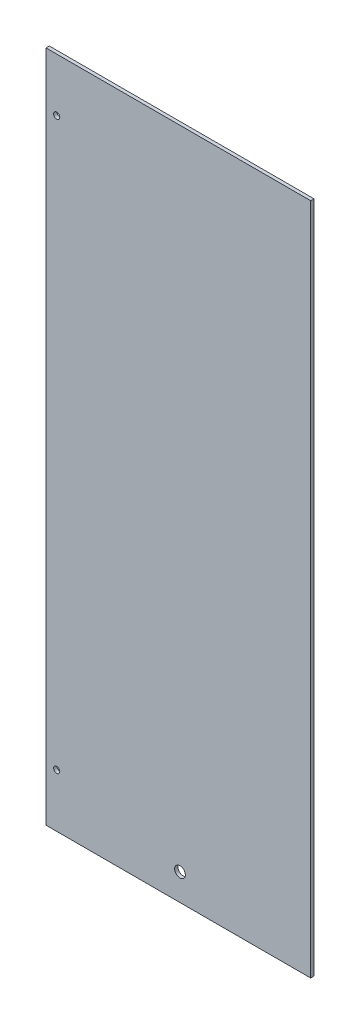
SolidWorks part; units mm, degrees
material "6061 Alloy"
ref_plane "Front" through (0, 0, 0) normal (0, 0, 1) x (1, 0, 0)
ref_plane "Top" through (0, 0, 0) normal (0, 1, 0) x (1, 0, 0)
ref_plane "Right" through (0, 0, 0) normal (1, 0, 0) x (0, 0, -1)
sketch "Sketch1" plane through (0, 0, 0) normal (0, 0, 1) x (1, 0, 0)
  line L1 (0, 0) -> (126.0475, 0)
  line L2 (0, 0) -> (0, 320.675)
  line L3 (0, 320.675) -> (126.0475, 320.675)
  line L4 (126.0475, 0) -> (126.0475, 320.675)
  dimension "D1" = 320.675
  dimension "D2" = 126.0475
extrude "Main Plate" add sketch "Sketch1" along normal blind 1.5875
sketch "Sketch2" plane through (0, 0, 1.5875) normal (0, 0, 1) x (1, 0, 0)
  line L0 (0, 320.675) -> (0, 0) construction
  line L1 (126.0475, 320.675) -> (0, 320.675) construction
  circle A0 centre (5.08, 295.275) radius 1.4605
  dimension "D3" = 2.921
  dimension "D1" = 5.08
  dimension "D2" = 25.4
extrude "Bolt Holes" cut sketch "Sketch2" against normal blind 6.35
pattern_linear "LPattern1" count 2 spacing 269.875 along (0, -1, 0) of "Bolt Holes"
sketch "Sketch3" plane through (0, 0, 1.5875) normal (0, 0, 1) x (1, 0, 0)
  line L0 (0, 320.675) -> (0, 0) construction
  line L1 (0, 0) -> (126.0475, 0) construction
  circle A0 centre (63.8175, 12.7) radius 2.54
  dimension "D1" = 5.08
  dimension "D2" = 63.8175
  dimension "D3" = 12.7
extrude "Wire Hole" cut sketch "Sketch3" against normal blind 6.35
